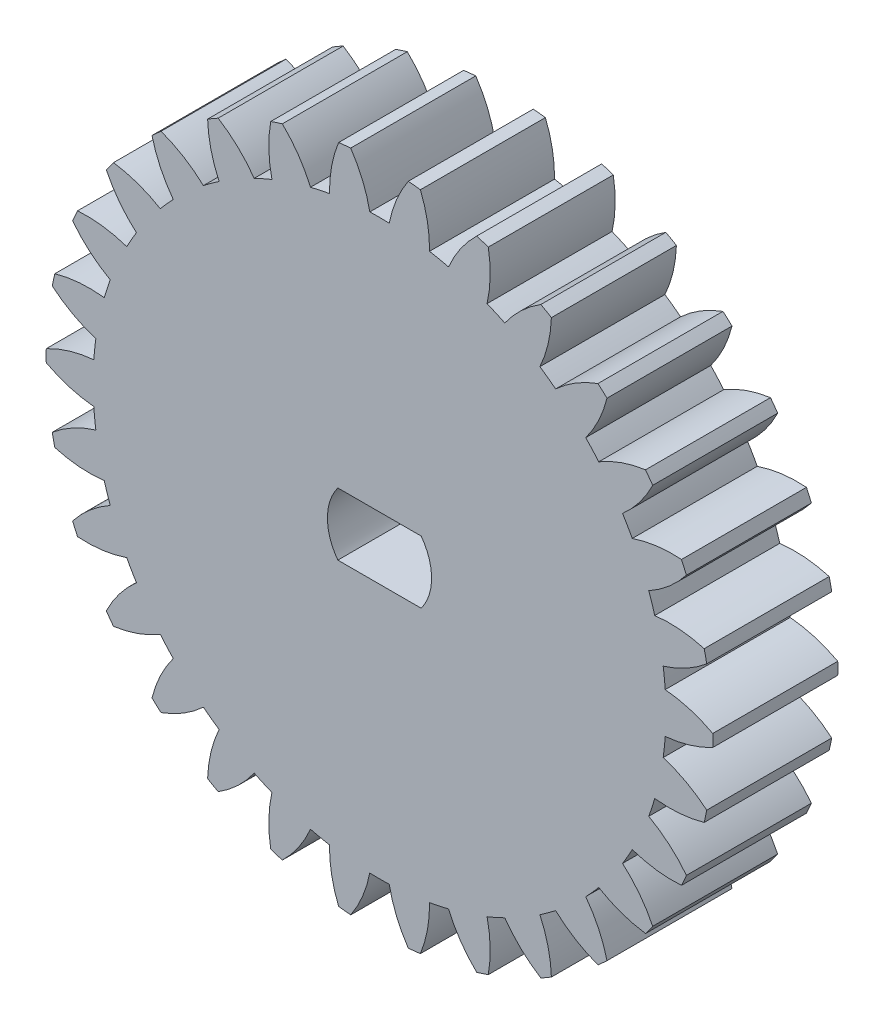
SolidWorks part; units mm, degrees
ref_plane "Front Plane" through (0, 0, 0) normal (0, 0, 1) x (1, 0, 0)
ref_plane "Top Plane" through (0, 0, 0) normal (0, 1, 0) x (1, 0, 0)
ref_plane "Right Plane" through (0, 0, 0) normal (1, 0, 0) x (0, 0, -1)
sketch "Sketch2" plane through (0, 0, 0) normal (0, 0, 1) x (1, 0, 0)
  line L0 (2, 1.5) -> (-2, 1.5)
  line L1 (-2, -1.5) -> (2, -1.5)
  line L4 (1.9494, 1.4) -> (-1.9494, 1.4)
  line L5 (-1.9494, -1.4) -> (1.9494, -1.4)
  circle A0 centre (0, 0) radius 0.4329 construction
  arc A241 (-2, 1.5) -> (-2, -1.5) centre (0, 0) ccw
  arc A242 (2, -1.5) -> (2, 1.5) centre (0, 0) ccw
  circle A965 centre (0, 0) radius 0.5
  arc A966 (-15.9973, -0.2927) -> (-13.7146, -0.9725) centre (-13.1775, 5.0034) ccw
  arc A967 (-13.7146, -0.9725) -> (-13.6171, -1.9002) centre (0, 0) ccw
  arc A968 (-13.6171, -1.9002) -> (-15.7086, -3.0398) centre (-11.8492, -7.6338) ccw
  arc A969 (-15.7086, -3.0398) -> (-15.5869, -3.6123) centre (0, 0) ccw
  arc A970 (-15.5869, -3.6123) -> (-13.2127, -3.8027) centre (-13.9298, 2.1543) ccw
  arc A971 (-13.2127, -3.8027) -> (-12.9244, -4.6898) centre (0, 0) ccw
  arc A972 (-12.9244, -4.6898) -> (-14.7333, -6.2393) centre (-10.0031, -9.9306) ccw
  arc A973 (-14.7333, -6.2393) -> (-14.4952, -6.7741) centre (0, 0) ccw
  arc A974 (-14.4952, -6.7741) -> (-12.1333, -6.4666) centre (-14.0733, -0.7889) ccw
  arc A975 (-12.1333, -6.4666) -> (-11.6669, -7.2745) centre (0, 0) ccw
  arc A976 (-11.6669, -7.2745) -> (-13.1141, -9.1662) centre (-7.7199, -11.7934) ccw
  arc A977 (-13.1141, -9.1662) -> (-12.7701, -9.6398) centre (0, 0) ccw
  arc A978 (-12.7701, -9.6398) -> (-10.5237, -8.848) centre (-13.6017, -3.6977) ccw
  arc A979 (-10.5237, -8.848) -> (-9.8995, -9.5412) centre (0, 0) ccw
  arc A980 (-9.8995, -9.5412) -> (-10.9218, -11.6925) centre (-5.0992, -13.1407) ccw
  arc A981 (-10.9218, -11.6925) -> (-10.4868, -12.0842) centre (0, 0) ccw
  arc A982 (-10.4868, -12.0842) -> (-8.4541, -10.8426) centre (-12.5357, -6.4448) ccw
  arc A983 (-8.4541, -10.8426) -> (-7.6995, -11.3909) centre (0, 0) ccw
  arc A984 (-7.6995, -11.3909) -> (-8.2521, -13.7078) centre (-2.2556, -13.9137) ccw
  arc A985 (-8.2521, -13.7078) -> (-7.7452, -14.0004) centre (0, 0) ccw
  arc A986 (-7.7452, -14.0004) -> (-6.0151, -12.3634) centre (-10.9218, -8.9103) ccw
  arc A987 (-6.0151, -12.3634) -> (-5.1629, -12.7428) centre (0, 0) ccw
  arc A988 (-5.1629, -12.7428) -> (-5.2218, -15.1239) centre (0.6865, -14.0787) ccw
  arc A989 (-5.2218, -15.1239) -> (-4.6651, -15.3048) centre (0, 0) ccw
  arc A990 (-4.6651, -15.3048) -> (-3.3131, -13.3438) centre (-8.8306, -10.9864) ccw
  arc A991 (-3.3131, -13.3438) -> (-2.4007, -13.5378) centre (0, 0) ccw
  arc A992 (-2.4007, -13.5378) -> (-1.9632, -15.8791) centre (3.5986, -13.6283) ccw
  arc A993 (-1.9632, -15.8791) -> (-1.3811, -15.9403) centre (0, 0) ccw
  arc A994 (-1.3811, -15.9403) -> (-0.4664, -13.7411) centre (-6.3534, -12.5823) ccw
  arc A995 (-0.4664, -13.7411) -> (0.4664, -13.7411) centre (0, 0) ccw
  arc A996 (0.4664, -13.7411) -> (1.3811, -15.9403) centre (6.3534, -12.5823) ccw
  arc A997 (1.3811, -15.9403) -> (1.9632, -15.8791) centre (0, 0) ccw
  arc A998 (1.9632, -15.8791) -> (2.4007, -13.5378) centre (-3.5986, -13.6283) ccw
  arc A999 (2.4007, -13.5378) -> (3.3131, -13.3438) centre (0, 0) ccw
  arc A1000 (3.3131, -13.3438) -> (4.6651, -15.3048) centre (8.8306, -10.9864) ccw
  arc A1001 (4.6651, -15.3048) -> (5.2218, -15.1239) centre (0, 0) ccw
  arc A1002 (5.2218, -15.1239) -> (5.1629, -12.7428) centre (-0.6865, -14.0787) ccw
  arc A1003 (5.1629, -12.7428) -> (6.0151, -12.3634) centre (0, 0) ccw
  arc A1004 (6.0151, -12.3634) -> (7.7452, -14.0004) centre (10.9218, -8.9103) ccw
  arc A1005 (7.7452, -14.0004) -> (8.2521, -13.7078) centre (0, 0) ccw
  arc A1006 (8.2521, -13.7078) -> (7.6995, -11.3909) centre (2.2556, -13.9137) ccw
  arc A1007 (7.6995, -11.3909) -> (8.4541, -10.8426) centre (0, 0) ccw
  arc A1008 (8.4541, -10.8426) -> (10.4868, -12.0842) centre (12.5357, -6.4448) ccw
  arc A1009 (10.4868, -12.0842) -> (10.9218, -11.6925) centre (0, 0) ccw
  arc A1010 (10.9218, -11.6925) -> (9.8995, -9.5412) centre (5.0992, -13.1407) ccw
  arc A1011 (9.8995, -9.5412) -> (10.5237, -8.848) centre (0, 0) ccw
  arc A1012 (10.5237, -8.848) -> (12.7701, -9.6398) centre (13.6017, -3.6977) ccw
  arc A1013 (12.7701, -9.6398) -> (13.1141, -9.1662) centre (0, 0) ccw
  arc A1014 (13.1141, -9.1662) -> (11.6669, -7.2745) centre (7.7199, -11.7934) ccw
  arc A1015 (11.6669, -7.2745) -> (12.1333, -6.4666) centre (0, 0) ccw
  arc A1016 (12.1333, -6.4666) -> (14.4952, -6.7741) centre (14.0733, -0.7889) ccw
  arc A1017 (14.4952, -6.7741) -> (14.7333, -6.2393) centre (0, 0) ccw
  arc A1018 (14.7333, -6.2393) -> (12.9244, -4.6898) centre (10.0031, -9.9306) ccw
  arc A1019 (12.9244, -4.6898) -> (13.2127, -3.8027) centre (0, 0) ccw
  arc A1020 (13.2127, -3.8027) -> (15.5869, -3.6123) centre (13.9298, 2.1543) ccw
  arc A1021 (15.5869, -3.6123) -> (15.7086, -3.0398) centre (0, 0) ccw
  arc A1022 (15.7086, -3.0398) -> (13.6171, -1.9002) centre (11.8492, -7.6338) ccw
  arc A1023 (13.6171, -1.9002) -> (13.7146, -0.9725) centre (0, 0) ccw
  arc A1024 (13.7146, -0.9725) -> (15.9973, -0.2927) centre (13.1775, 5.0034) ccw
  arc A1025 (15.9973, -0.2927) -> (15.9973, 0.2927) centre (0, 0) ccw
  arc A1026 (15.9973, 0.2927) -> (13.7146, 0.9725) centre (13.1775, -5.0034) ccw
  arc A1027 (13.7146, 0.9725) -> (13.6171, 1.9002) centre (0, 0) ccw
  arc A1028 (13.6171, 1.9002) -> (15.7086, 3.0398) centre (11.8492, 7.6338) ccw
  arc A1029 (15.7086, 3.0398) -> (15.5869, 3.6123) centre (0, 0) ccw
  arc A1030 (15.5869, 3.6123) -> (13.2127, 3.8027) centre (13.9298, -2.1543) ccw
  arc A1031 (13.2127, 3.8027) -> (12.9244, 4.6898) centre (0, 0) ccw
  arc A1032 (12.9244, 4.6898) -> (14.7333, 6.2393) centre (10.0031, 9.9306) ccw
  arc A1033 (14.7333, 6.2393) -> (14.4952, 6.7741) centre (0, 0) ccw
  arc A1034 (14.4952, 6.7741) -> (12.1333, 6.4666) centre (14.0733, 0.7889) ccw
  arc A1035 (12.1333, 6.4666) -> (11.6669, 7.2745) centre (0, 0) ccw
  arc A1036 (11.6669, 7.2745) -> (13.1141, 9.1662) centre (7.7199, 11.7934) ccw
  arc A1037 (13.1141, 9.1662) -> (12.7701, 9.6398) centre (0, 0) ccw
  arc A1038 (12.7701, 9.6398) -> (10.5237, 8.848) centre (13.6017, 3.6977) ccw
  arc A1039 (10.5237, 8.848) -> (9.8995, 9.5412) centre (0, 0) ccw
  arc A1040 (9.8995, 9.5412) -> (10.9218, 11.6925) centre (5.0992, 13.1407) ccw
  arc A1041 (10.9218, 11.6925) -> (10.4868, 12.0842) centre (0, 0) ccw
  arc A1042 (10.4868, 12.0842) -> (8.4541, 10.8426) centre (12.5357, 6.4448) ccw
  arc A1043 (8.4541, 10.8426) -> (7.6995, 11.3909) centre (0, 0) ccw
  arc A1044 (7.6995, 11.3909) -> (8.2521, 13.7078) centre (2.2556, 13.9137) ccw
  arc A1045 (8.2521, 13.7078) -> (7.7452, 14.0004) centre (0, 0) ccw
  arc A1046 (7.7452, 14.0004) -> (6.0151, 12.3634) centre (10.9218, 8.9103) ccw
  arc A1047 (6.0151, 12.3634) -> (5.1629, 12.7428) centre (0, 0) ccw
  arc A1048 (5.1629, 12.7428) -> (5.2218, 15.1239) centre (-0.6865, 14.0787) ccw
  arc A1049 (5.2218, 15.1239) -> (4.6651, 15.3048) centre (0, 0) ccw
  arc A1050 (4.6651, 15.3048) -> (3.3131, 13.3438) centre (8.8306, 10.9864) ccw
  arc A1051 (3.3131, 13.3438) -> (2.4007, 13.5378) centre (0, 0) ccw
  arc A1052 (2.4007, 13.5378) -> (1.9632, 15.8791) centre (-3.5986, 13.6283) ccw
  arc A1053 (1.9632, 15.8791) -> (1.3811, 15.9403) centre (0, 0) ccw
  arc A1054 (1.3811, 15.9403) -> (0.4664, 13.7411) centre (6.3534, 12.5823) ccw
  arc A1055 (0.4664, 13.7411) -> (-0.4664, 13.7411) centre (0, 0) ccw
  arc A1056 (-0.4664, 13.7411) -> (-1.3811, 15.9403) centre (-6.3534, 12.5823) ccw
  arc A1057 (-1.3811, 15.9403) -> (-1.9632, 15.8791) centre (0, 0) ccw
  arc A1058 (-1.9632, 15.8791) -> (-2.4007, 13.5378) centre (3.5986, 13.6283) ccw
  arc A1059 (-2.4007, 13.5378) -> (-3.3131, 13.3438) centre (0, 0) ccw
  arc A1060 (-3.3131, 13.3438) -> (-4.6651, 15.3048) centre (-8.8306, 10.9864) ccw
  arc A1061 (-4.6651, 15.3048) -> (-5.2218, 15.1239) centre (0, 0) ccw
  arc A1062 (-5.2218, 15.1239) -> (-5.1629, 12.7428) centre (0.6865, 14.0787) ccw
  arc A1063 (-5.1629, 12.7428) -> (-6.0151, 12.3634) centre (0, 0) ccw
  arc A1064 (-6.0151, 12.3634) -> (-7.7452, 14.0004) centre (-10.9218, 8.9103) ccw
  arc A1065 (-7.7452, 14.0004) -> (-8.2521, 13.7078) centre (0, 0) ccw
  arc A1066 (-8.2521, 13.7078) -> (-7.6995, 11.3909) centre (-2.2556, 13.9137) ccw
  arc A1067 (-7.6995, 11.3909) -> (-8.4541, 10.8426) centre (0, 0) ccw
  arc A1068 (-8.4541, 10.8426) -> (-10.4868, 12.0842) centre (-12.5357, 6.4448) ccw
  arc A1069 (-10.4868, 12.0842) -> (-10.9218, 11.6925) centre (0, 0) ccw
  arc A1070 (-10.9218, 11.6925) -> (-9.8995, 9.5412) centre (-5.0992, 13.1407) ccw
  arc A1071 (-9.8995, 9.5412) -> (-10.5237, 8.848) centre (0, 0) ccw
  arc A1072 (-10.5237, 8.848) -> (-12.7701, 9.6398) centre (-13.6017, 3.6977) ccw
  arc A1073 (-12.7701, 9.6398) -> (-13.1141, 9.1662) centre (0, 0) ccw
  arc A1074 (-13.1141, 9.1662) -> (-11.6669, 7.2745) centre (-7.7199, 11.7934) ccw
  arc A1075 (-11.6669, 7.2745) -> (-12.1333, 6.4666) centre (0, 0) ccw
  arc A1076 (-12.1333, 6.4666) -> (-14.4952, 6.7741) centre (-14.0733, 0.7889) ccw
  arc A1077 (-14.4952, 6.7741) -> (-14.7333, 6.2393) centre (0, 0) ccw
  arc A1078 (-14.7333, 6.2393) -> (-12.9244, 4.6898) centre (-10.0031, 9.9306) ccw
  arc A1079 (-12.9244, 4.6898) -> (-13.2127, 3.8027) centre (0, 0) ccw
  arc A1080 (-13.2127, 3.8027) -> (-15.5869, 3.6123) centre (-13.9298, -2.1543) ccw
  arc A1081 (-15.5869, 3.6123) -> (-15.7086, 3.0398) centre (0, 0) ccw
  arc A1082 (-15.7086, 3.0398) -> (-13.6171, 1.9002) centre (-11.8492, 7.6338) ccw
  arc A1083 (-13.6171, 1.9002) -> (-13.7146, 0.9725) centre (0, 0) ccw
  arc A1084 (-13.7146, 0.9725) -> (-15.9973, 0.2927) centre (-13.1775, -5.0034) ccw
  arc A1085 (-15.9973, 0.2927) -> (-15.9973, -0.2927) centre (0, 0) ccw
  arc A1086 (1.9494, -1.4) -> (1.9494, 1.4) centre (0, 0) ccw
  arc A1087 (-1.9494, 1.4) -> (-1.9494, -1.4) centre (0, 0) ccw
  dimension "D1" = 5
  dimension "D2" = 3
  dimension "D3" = 1.5
  dimension "D4" = 0.1
extrude "Boss-Extrude1" add sketch "Sketch2" along normal blind 6 contours A1084 A1085 A966 A967 A968 A969 A970 A971 A972 A973 A974 A975 A976 A977 A978 A979 A980 A981 A982 A983 A984 A985 A986 A987 A988 A989 A990 A991 A992 A993 A994 A995 A996 A997 A998 A999 A1000 A1001 A1002 A1003 A1004 A1005 A1006 A1007 A1008 A1009 A1010 A1011 A1012 A1013 A1014 region at (-15.5483, 0, 0)
